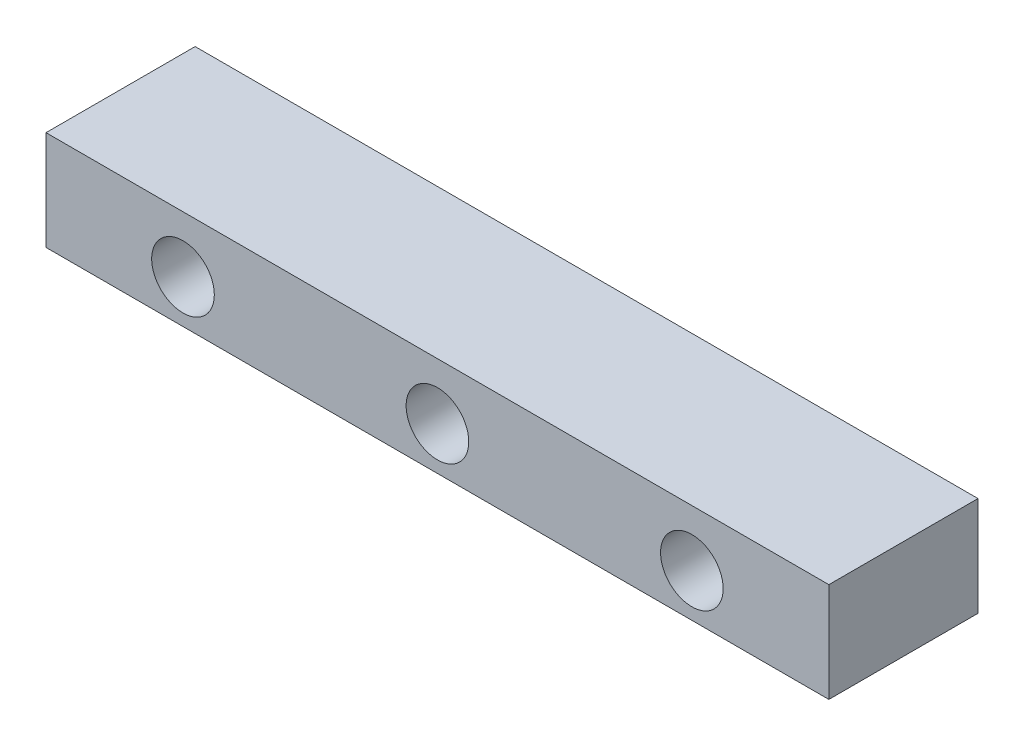
SolidWorks part; units mm, degrees
ref_plane "Front Plane" through (0, 0, 0) normal (0, 0, 1) x (1, 0, 0)
ref_plane "Top Plane" through (0, 0, 0) normal (0, 1, 0) x (1, 0, 0)
ref_plane "Right Plane" through (0, 0, 0) normal (1, 0, 0) x (0, 0, -1)
sketch "Sketch1" plane through (0, 0, 0) normal (0, 1, 0) x (1, 0, 0)
  line L1 (0, 0) -> (400, 0)
  line L2 (0, 0) -> (0, 76.2)
  line L3 (0, 76.2) -> (400, 76.2)
  line L4 (400, 0) -> (400, 76.2)
  dimension "D1" = 400
  dimension "D2" = 76.2
extrude "Boss-Extrude1" add sketch "Sketch1" along normal blind 50.8
sketch "Sketch2" plane through (0, 0, 0) normal (0, 0, 1) x (1, 0, 0)
  line L0 (70, 22) -> (200, 22)
  line L1 (0, 0) -> (70, 0)
  line L2 (0, 0) -> (0, 22)
  line L3 (0, 22) -> (70, 22)
  line L4 (70, 0) -> (70, 22)
  line L5 (200, 22) -> (330, 22)
  circle A0 centre (70, 22) radius 16
  circle A1 centre (200, 22) radius 16
  circle A2 centre (330, 22) radius 16
  dimension "D1" = 70
  dimension "D2" = 22
  dimension "D3" = 130
  dimension "D4" = 130
extrude "Cut-Extrude1" cut sketch "Sketch2" against normal blind 76.2 contours A0 | A1 | A2
